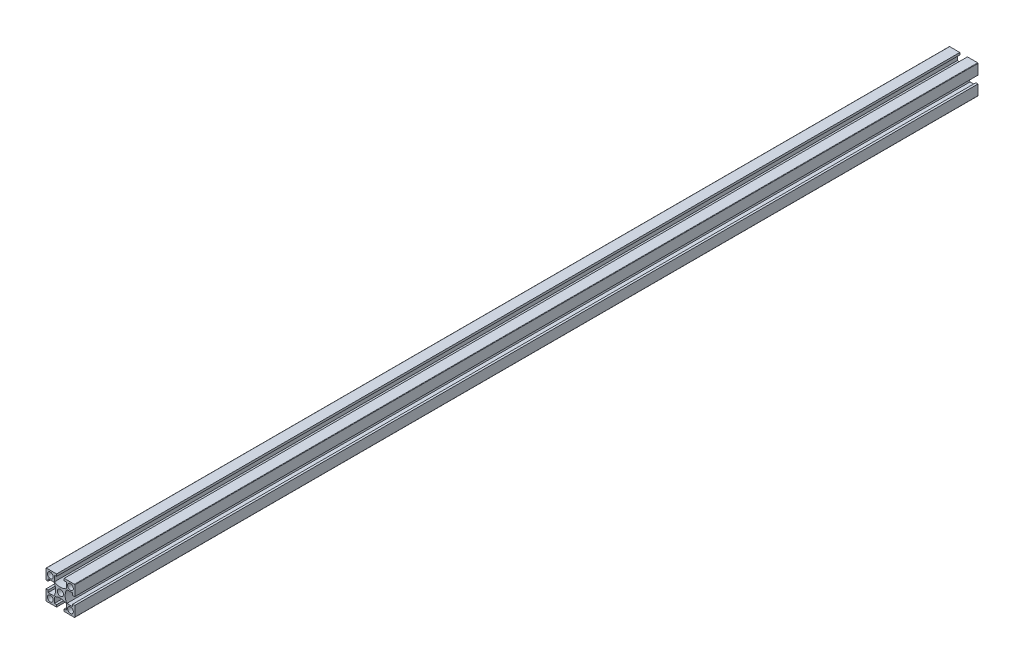
SolidWorks part; units mm, degrees
ref_plane "정면" through (0, 0, 0) normal (0, 0, 1) x (1, 0, 0)
ref_plane "윗면" through (0, 0, 0) normal (0, 1, 0) x (1, 0, 0)
ref_plane "우측면" through (0, 0, 0) normal (1, 0, 0) x (0, 0, -1)
sketch "스케치1" plane through (0, 0, 0) normal (0, 0, 1) x (1, 0, 0)
  line L0 (0, 32.0265) -> (0, -31.6588) construction
  line L1 (-10, 10) -> (-10, -10)
  line L2 (-10, 10) -> (10, 10)
  line L3 (-10, 2.65) -> (-8.5, 2.65)
  line L4 (13.6618, 0) -> (-11.6993, 0) construction
  line L5 (-8.5, 2.65) -> (-8.5, 4.15)
  line L6 (-8.5, 4.15) -> (-4.5032, 4.15)
  line L7 (-10, -2.65) -> (-8.5, -2.65)
  line L8 (-8.5, -2.65) -> (-8.5, -4.15)
  line L9 (-8.5, -4.15) -> (-4.5032, -4.15)
  line L10 (-10, -10) -> (10, -10)
  line L11 (10, 10) -> (10, -10)
  circle A0 centre (-7, 7) radius 2
  circle A1 centre (-7, -7) radius 2
  arc A2 (-4.5032, 4.15) -> (-4.5032, -4.15) centre (-11.0587, 0) cw
  circle A3 centre (0, 0) radius 2.15
  circle A4 centre (7, 7) radius 2
  circle A5 centre (7, -7) radius 2
  point P21 (-10, 0)
  point P23 (-3.3, 0)
  point P31 (0, -10)
  point P32 (0, 10)
  dimension "D3" = 4
  dimension "D9" = 6.7
  dimension "D10" = 4.3
  dimension "D11" = 7.7587
  dimension "D1" = 20
  dimension "D2" = 20
  dimension "D4" = 14
  dimension "D5" = 14
  dimension "D6" = 5.3
  dimension "D7" = 8.3
  dimension "D8" = 1.5
extrude "보스-돌출1" add sketch "스케치1" along normal blind 628 contours A0 | A4 | A3 | A5 | A1 | A2 L6 L5 L3 L1 L7 L8 L9 | L2 L11 L10 L1 region at (-6.6069, 0, 0) region at (-7, 7, 0) region at (-7, -7, 0) region at (0, 0, 0) region at (7, 7, 0) region at (7, -7, 0)
extrude "컷-돌출1" cut sketch "스케치1<3>" along normal up to next contours A2 L6 L5 L3 L1 L7 L8 L9 region at (-6.6069, 0, 0)
sketch "스케치1<3>" plane through (0, 0, 0) normal (0, 0, 1) x (1, 0, 0) same geometry as "스케치1"
pattern_circular "원형 패턴1" count 4 over 360 about axis through (0, 0, 628) along (0, 0, -1) of "컷-돌출1" reverse direction yes
fillet "필렛1" radius 0.3 4 edges at (10, -10, 314) (-10, -10, 314) (-10, 10, 314) (10, 10, 314)
sketch "스케치2" plane through (0, 0, 0) normal (1, 0, 0) x (0, 0, -1)
  line L2 (0, -2.65) -> (0, -9.7) construction
  circle A0 centre (-15, 0) radius 2.5
  dimension "D2" = 5
  dimension "D1" = 15
extrude "컷-돌출2" cut sketch "스케치2" against normal through all both and the other way through all
